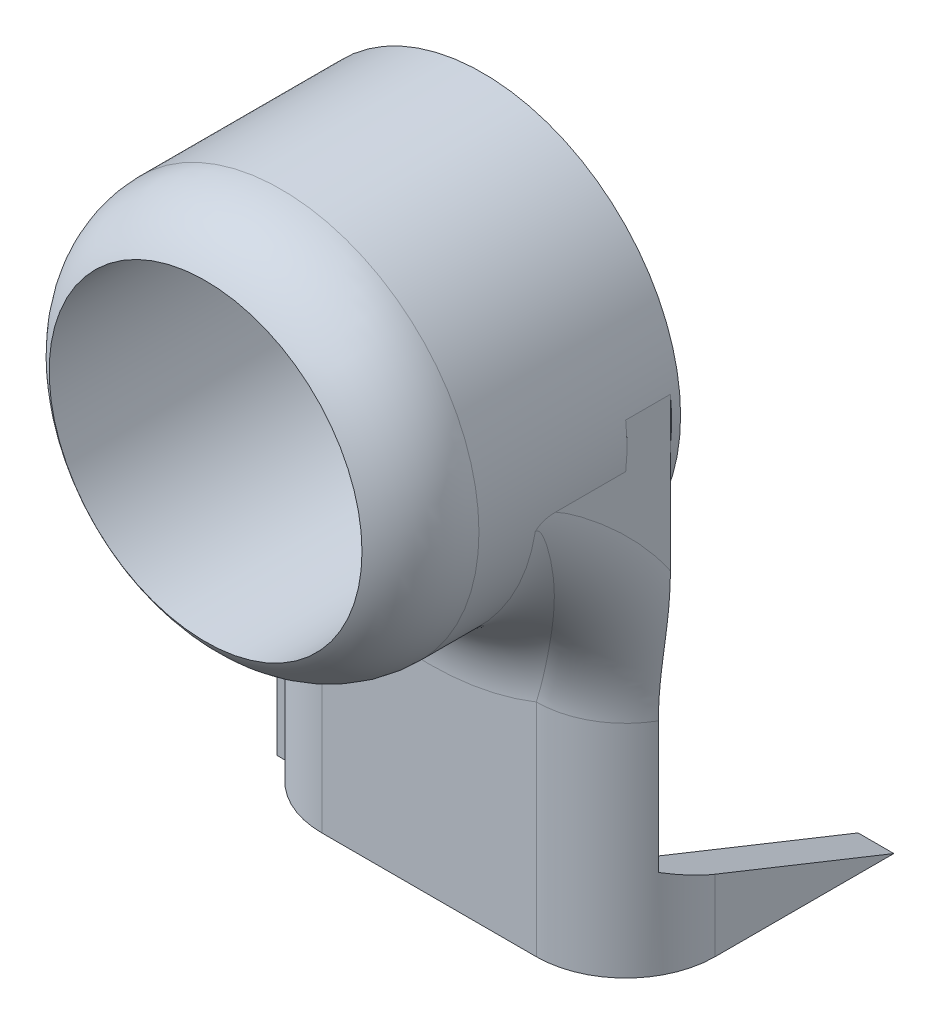
SolidWorks part; units mm, degrees
material "ABS"
ref_plane "Plan de face" through (0, 0, 0) normal (0, 0, 1) x (1, 0, 0)
ref_plane "Plan de dessus" through (0, 0, 0) normal (0, 1, 0) x (1, 0, 0)
ref_plane "Plan de droite" through (0, 0, 0) normal (1, 0, 0) x (0, 0, -1)
sketch "Esquisse1" plane through (0, 0, 0) normal (0, 0, 1) x (1, 0, 0)
  line L0 (0, 0) -> (0, -57)
  line L1 (0, -57) -> (44, -57)
  line L2 (44, -57) -> (44, 0)
  arc A0 (0, 0) -> (44, 0) centre (22, -2.5) cw
  circle A1 centre (22, -2.5) radius 17.5
  dimension "D4" = 35
  dimension "D1" = 57
  dimension "D2" = 44
  dimension "D3" = 2.5
extrude "Boss.-Extru.1" add sketch "Esquisse1" along normal blind 5
sketch "Esquisse2" plane through (0, 0, 5) normal (0, 0, 1) x (1, 0, 0)
  circle A0 centre (22, -2.5) radius 17.5
  circle A1 centre (22, -2.5) radius 22.1416
extrude "Boss.-Extru.2" add sketch "Esquisse2" along normal blind 25
fillet "Congé1" radius 10 1 edges at (22, -24.6416, 5)
sketch "Esquisse3" plane through (44, 0, 0) normal (1, 0, 0) x (0, 0, -1)
  line L0 (0, -47) -> (25, -57)
  line L1 (0, -57) -> (0, 0) construction
  line L2 (25, -57) -> (0, -57)
  line L3 (0, -57) -> (0, -47)
  dimension "D1" = 10
  dimension "D2" = 25
extrude "Boss.-Extru.3" add sketch "Esquisse3" against normal blind 4
sketch "Esquisse4" plane through (0, 0, 0) normal (-1, 0, 0) x (0, 0, 1)
  line L0 (0, -57) -> (-25, -57)
  line L1 (-25, -57) -> (0, -47)
  line L2 (0, 0) -> (0, -57) construction
  line L3 (0, -47) -> (0, -57)
  dimension "D1" = 10
  dimension "D2" = 25
extrude "Boss.-Extru.4" add sketch "Esquisse4" against normal blind 4 separate body
sketch "Esquisse5" plane through (0, 0, 0) normal (0, 0, -1) x (-1, 0, 0)
  circle A0 centre (-22, -2.5) radius 22.1416
extrude "Boss.-Extru.5" add sketch "Esquisse5" along normal blind 1
sketch "Esquisse6" plane through (0, 0, -1) normal (0, 0, -1) x (-1, 0, 0)
  line L0 (-22, -2.5) -> (-12.36, -2.5) construction
  circle A0 centre (-12.36, -2.5) radius 1.25
  circle A1 centre (-22, -12.14) radius 1.25
  circle A2 centre (-31.64, -2.5) radius 1.25
  circle A3 centre (-22, 7.14) radius 1.25
  point P13 (-22, -2.5)
  dimension "D2" = 2.5
  dimension "D1" = 9.64
  dimension "D3" = 4
extrude "Enlèv. mat.-Extru.1" cut sketch "Esquisse6" against normal through all
fillet "Congé2" radius 10 1 edges at (44.1416, -2.5, 30)
fillet "Congé3" radius 10 4 edges at (0, -6.3239, 13.0687) (44, -7.0238, 12.4955) (0, -41.4662, 5) (44, -41.4662, 5)
sketch "Esquisse7" plane through (0, 0, -1) normal (0, 0, -1) x (-1, 0, 0)
  arc A2 (-24, 11) -> (-13.3073, 8.4182) centre (-20.6138, 1.5908) cw construction
  circle A3 centre (-24, 11) radius 2 construction
  circle A4 centre (-13.3073, 8.4182) radius 2 construction
  arc A5 (-25.1282, 12.6514) -> (-11.6577, 9.5491) centre (-20.0149, 4.0576) cw
  arc A6 (-25.1282, 12.6514) -> (-24, 9) centre (-24, 11) ccw
  arc A7 (-11.6577, 9.5491) -> (-13.9308, 6.5179) centre (-13.3073, 8.4182) cw
  arc A8 (-13.9308, 6.5179) -> (-24, 9) centre (-29.1771, -33.6668) ccw
  point P6 (0, 0)
  point P17 (-13.9308, 6.5179)
  dimension "D4" = 10
  dimension "D6" = 4
  dimension "D7" = 10
  dimension "D1" = 58
  dimension "D2" = 16
  dimension "D3" = 11
  dimension "D5" = 42
extrude "Enlèv. mat.-Extru.2" cut sketch "Esquisse7" against normal through all
